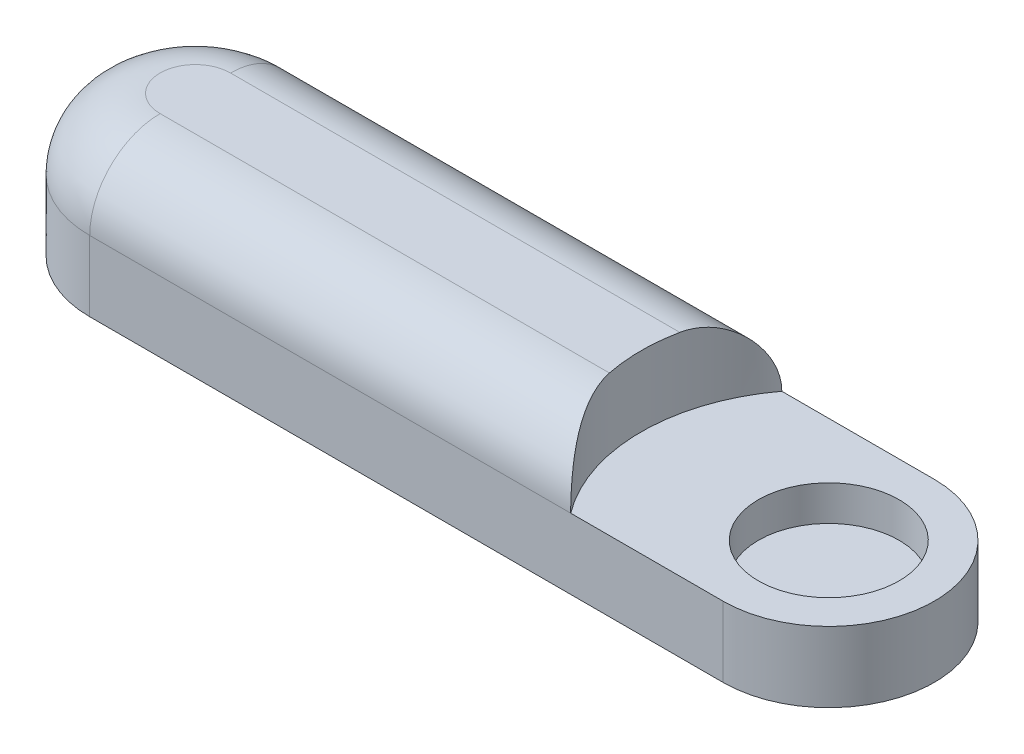
SolidWorks part; units mm, degrees
material "6061-T6 (SS)"
ref_plane "Ebene vorne" through (0, 0, 0) normal (0, 0, 1) x (1, 0, 0)
ref_plane "Ebene oben" through (0, 0, 0) normal (0, 1, 0) x (1, 0, 0)
ref_plane "Ebene rechts" through (0, 0, 0) normal (1, 0, 0) x (0, 0, -1)
sketch "Skizze3" plane through (0, 0, 0) normal (0, 1, 0) x (1, 0, 0)
  line L1 (0, -45) -> (-270, -45)
  line L3 (0, 45) -> (-270, 45)
  arc A0 (0, -45) -> (0, 45) centre (0, 0) ccw
  arc A1 (-270, 45) -> (-270, -45) centre (-270, 0) ccw
  dimension "D1" = 45
  dimension "D3" = 45
  dimension "D2" = 270
  dimension "D4" = 90
extrude "Aufsatz-Linear austragen1" add sketch "Skizze3" along normal blind 30 and the other way blind 30
sketch "Skizze4" plane through (0, 0, 45) normal (0, 0, 1) x (1, 0, 0)
  line L1 (45, 30) -> (-5, 30)
  line L2 (45, 30) -> (45, 0)
  line L3 (45, 0) -> (-5, 0)
  line L4 (-5, 30) -> (-5, 0)
  dimension "D1" = 50
  dimension "D2" = 30
extrude "Schnitt-Linear austragen1" cut sketch "Skizze4" against normal up to surface (90 mm away) up to face at (-135, 0, -45)
sketch "Skizze5" plane through (0, 0, 0) normal (0, 1, 0) x (1, 0, 0)
  circle A0 centre (0, 0) radius 30
  dimension "D1" = 60
extrude "Schnitt-Linear austragen2" cut sketch "Skizze5" against normal blind 15
sketch "Skizze6" plane through (0, 30, 0) normal (0, 1, 0) x (1, 0, 0)
  line L0 (-5, 45) -> (-5, -45) construction
  line L1 (-5, 75) -> (-5, -75)
  arc A0 (-5, 75) -> (-5, -75) centre (-5, 0) ccw
  dimension "D1" = 150
extrude "Schnitt-Linear austragen3" cut sketch "Skizze6" against normal up to surface (30 mm away) up to face at (10, 0, 0)
sketch "Skizze9" plane through (0, -30, 0) normal (0, -1, 0) x (1, 0, 0)
  circle A0 centre (-305, 0) radius 10
  arc A1 (-270, 45) -> (-270, -45) centre (-270, 0) ccw construction
  dimension "D1" = 20
  dimension "D2" = 35
extrude "Aufsatz-Linear austragen3" add sketch "Skizze9" along normal blind 35
fillet "Verrundung2" radius 10 1 edges at (-305, -30, -10)
fillet "Verrundung3" radius 30 3 edges at (-167.5, 30, -45) (-167.5, 30, 45) (-315, 30, 0)
